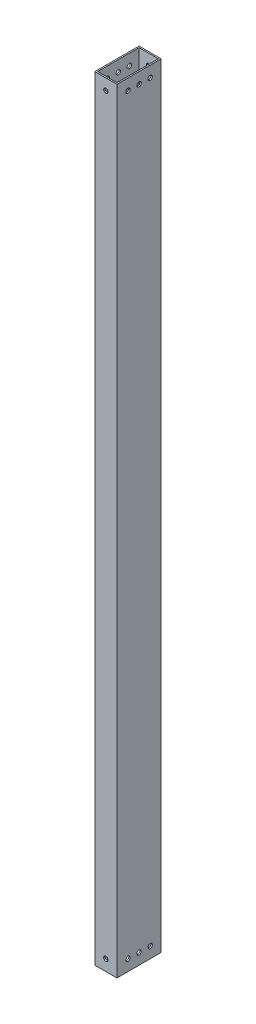
SolidWorks part; units mm, degrees
material "6061-T6 (SS)"
ref_plane "Front" through (0, 0, 0) normal (0, 0, 1) x (1, 0, 0)
ref_plane "Top" through (0, 0, 0) normal (0, 1, 0) x (1, 0, 0)
ref_plane "Right" through (0, 0, 0) normal (1, 0, 0) x (0, 0, -1)
sketch "Sketch1" plane through (0, 0, 0) normal (0, 1, 0) x (1, 0, 0)
  line L1 (12.7, 25.4) -> (-12.7, 25.4)
  line L2 (12.7, 25.4) -> (12.7, -25.4)
  line L3 (12.7, -25.4) -> (-12.7, -25.4)
  line L4 (-12.7, 25.4) -> (-12.7, -25.4)
  line L5 (12.7, 25.4) -> (-12.7, -25.4) construction
  line L6 (12.7, -25.4) -> (-12.7, 25.4) construction
  point P0 (0, 0)
  dimension "D1" = 25.4
  dimension "D2" = 50.8
extrude "Extrude-Thin1" add sketch "Sketch1" along normal blind 889 thin thin type one direction reverse wall 1.5875
sketch "Sketch4" plane through (-12.7, 0, 0) normal (-1, 0, 0) x (0, 0, 1)
  line L0 (-12.7, 876.3) -> (12.7, 876.3) construction
  line L2 (-25.4, 889) -> (25.4, 889) construction
  line L3 (-12.7, 12.7) -> (12.7, 12.7) construction
  line L5 (-25.4, 0) -> (25.4, 0) construction
  point P0 (-12.7, 876.3)
  point P2 (0, 876.3)
  point P4 (12.7, 876.3)
  point P15 (-12.7, 12.7)
  point P17 (0, 12.7)
  point P19 (12.7, 12.7)
  point P26 (0, 0)
  dimension "D1" = 12.7
  dimension "D2" = 12.7
  dimension "D3" = 12.7
  dimension "D4" = 12.7
hole_wizard "#10 Clearance Hole1" positions "Sketch4" profile "Sketch3" hole size "#10" standard "ANSI Inch" end condition through all
sketch "Sketch3" plane through (-12.7, 876.3, -12.7) normal (0, 1, 0) x (0, 0, 1)
  line L0 (0, 0) -> (0, 25.4)
  line L1 (0, 25.4) -> (2.5527, 25.4)
  line L2 (2.5527, 25.4) -> (2.5527, 0)
  line L5 (2.5527, 0) -> (0, 0)
  line L11 (0, -6.35) -> (0, 107.95) construction
  dimension "Thru Hole Dia." = 5.1054
  dimension "Thru Hole Depth" = 25.4
sketch "Sketch7" plane through (0, 0, 25.4) normal (0, 0, 1) x (1, 0, 0)
  line L0 (-12.7, 0) -> (12.7, 0) construction
  line L1 (-12.7, 889) -> (12.7, 889) construction
  point P0 (0, 876.3)
  point P2 (0, 12.7)
  dimension "D1" = 12.7
  dimension "D2" = 12.7
hole_wizard "#10 Clearance Hole2" positions "Sketch7" profile "Sketch6" hole size "#10" standard "ANSI Inch" end condition through all
sketch "Sketch6" plane through (0, 876.3, 25.4) normal (1, 0, 0) x (0, -1, 0)
  line L0 (0, 0) -> (0, 50.8)
  line L1 (0, 50.8) -> (2.5527, 50.8)
  line L2 (2.5527, 50.8) -> (2.5527, 0)
  line L5 (2.5527, 0) -> (0, 0)
  line L11 (0, -6.35) -> (0, 107.95) construction
  dimension "Thru Hole Dia." = 5.1054
  dimension "Thru Hole Depth" = 50.8
